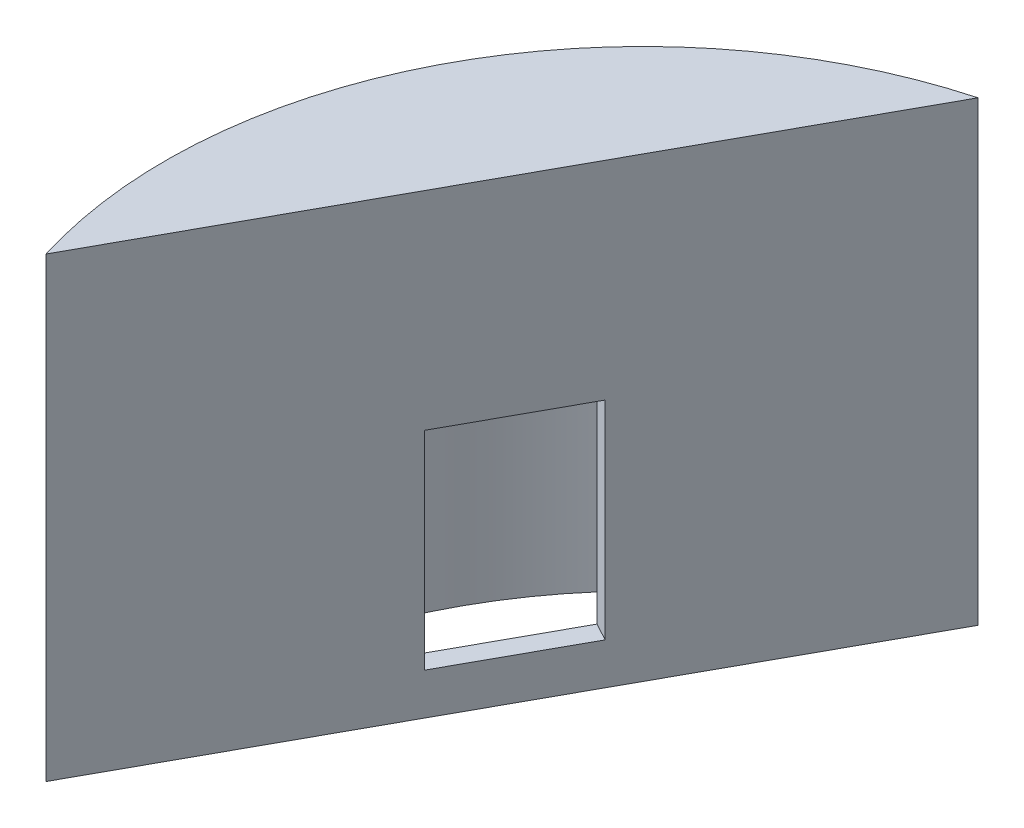
SolidWorks part; units mm, degrees
ref_plane "Front Plane" through (0, 0, 0) normal (0, 0, 1) x (1, 0, 0)
ref_plane "Top Plane" through (0, 0, 0) normal (0, 1, 0) x (1, 0, 0)
ref_plane "Right Plane" through (0, 0, 0) normal (1, 0, 0) x (0, 0, -1)
sketch "Sketch1" plane through (0, 0, 0) normal (0, 1, 0) x (1, 0, 0)
  circle A0 centre (0, 0) radius 69.85
  circle A1 centre (0, 0) radius 73.025
  dimension "D1" = 139.7
  dimension "D2" = 146.05
extrude "Boss-Extrude1" add sketch "Sketch1" along normal blind 63.5
sketch "Sketch2" plane through (0, 0, 0) normal (0, -1, 0) x (1, 0, 0)
  circle A0 centre (0, 0) radius 73.025
  dimension "D1" = 146.05
extrude "Boss-Extrude2" add sketch "Sketch2" along normal blind 6.35
sketch "Sketch3" plane through (0, 0, 0) normal (0, 1, 0) x (1, 0, 0)
  line L1 (-67.6153, -17.527) -> (-21.4092, 66.4881)
  circle A1 centre (0, 0) radius 69.85 construction
  arc A2 (-21.4092, 66.4881) -> (-67.6153, -17.527) centre (0, 0) ccw
  point P8 (0, 0)
  point P10 (-69.7753, -21.542)
  dimension "D1" = 50.8
extrude "Boss-Extrude3" add sketch "Sketch3" along normal blind 63.5
sketch "Sketch4" plane through (0, 63.5, 0) normal (0, 1, 0) x (1, 0, 0)
  line L0 (-25.7919, 64.9138) -> (-68.6329, -12.9827)
  line L1 (-67.6153, -17.527) -> (-21.4092, 66.4881) construction
  arc A0 (-25.7919, 64.9138) -> (-68.6329, -12.9827) centre (0, 0) ccw
  dimension "D2" = 69.85
  dimension "D1" = 88.9
extrude "Cut-Extrude2" cut sketch "Sketch4" against normal blind 69.85 from offset 6.35 offset against normal yes
ref_plane "Plane1" through (-42.2867, 0, -23.2565) normal (0.8762, 0, 0.4819) x (0.4819, 0, -0.8762)
sketch "Sketch6" plane through (-42.2867, 0, -23.2565) normal (0.8762, 0, 0.4819) x (0.4819, 0, -0.8762)
  line L0 (-47.9414, 0) -> (47.9414, 0) construction
  line L5 (-9.8414, 31.75) -> (10.4786, 31.75)
  line L6 (-9.8414, 31.75) -> (-9.8414, 0)
  line L7 (-9.8414, 0) -> (10.4786, 0)
  line L8 (10.4786, 31.75) -> (10.4786, 0)
  line L19 (-47.9414, 63.5) -> (-47.9414, 0) construction
  dimension "D1" = 38.1
  dimension "D2" = 31.75
  dimension "D6" = 20.32
extrude "Cut-Extrude4" cut sketch "Sketch6" against normal blind 31.75 from offset 19.05
sketch "Sketch7" plane through (0, 63.5, 0) normal (0, 1, 0) x (1, 0, 0)
  line L0 (-72.6096, -26.608) -> (-10.1714, 86.9215)
  line L1 (-10.1714, 86.9215) -> (114.9599, 65.8058)
  line L2 (114.9599, 65.8058) -> (122.5488, -33.7487)
  line L3 (122.5488, -33.7487) -> (41.0179, -93.9807)
  line L4 (41.0179, -93.9807) -> (-75.6034, -72.6768)
  line L5 (-75.6034, -72.6768) -> (-72.6096, -26.608)
  line L6 (-67.6153, -17.527) -> (-21.4092, 66.4881) construction
  point P8 (-70.9669, -27.2198)
  point P9 (41.0179, -93.9807)
extrude "Cut-Extrude5" cut sketch "Sketch7" against normal blind 1016
